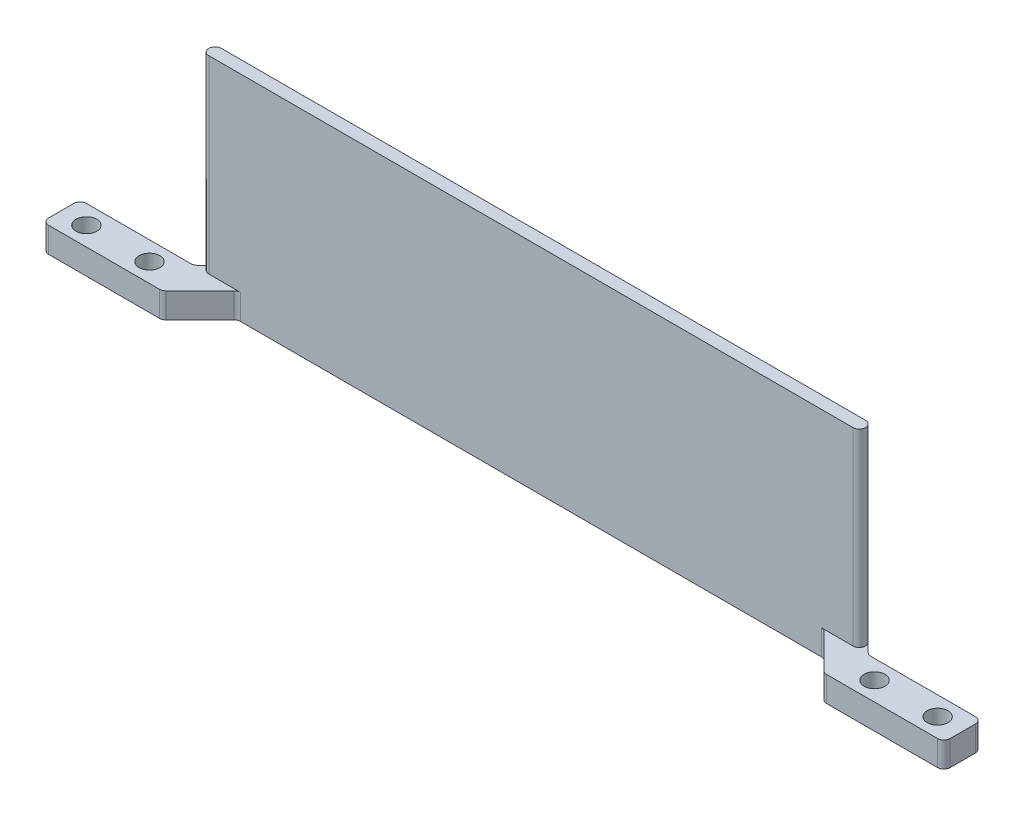
SolidWorks part; units mm, degrees
ref_plane "前视基准面" through (0, 0, 0) normal (0, 0, 1) x (1, 0, 0)
ref_plane "上视基准面" through (0, 0, 0) normal (0, 1, 0) x (1, 0, 0)
ref_plane "右视基准面" through (0, 0, 0) normal (1, 0, 0) x (0, 0, -1)
other "Configuration Table"
sketch "草图1" plane through (0, 0, 0) normal (0, 1, 0) x (1, 0, 0)
  line L0 (0, 0) -> (0, 13.6735) construction
  line L1 (-71.5, 3) -> (-71.5, -3)
  line L2 (-71.5, -3) -> (-52.5, -3)
  line L3 (-52.5, -3) -> (-46.5, 3)
  line L4 (-46.5, 3) -> (46.5, 3)
  line L5 (-51.5, 5) -> (51.5, 5)
  line L6 (-71.5, 3) -> (-53.5, 3)
  line L7 (51.5, 5) -> (53.5, 3)
  line L8 (-51.5, 5) -> (-53.5, 3)
  line L9 (71.5, 3) -> (53.5, 3)
  line L10 (52.5, -3) -> (46.5, 3)
  line L11 (71.5, -3) -> (52.5, -3)
  line L12 (71.5, 3) -> (71.5, -3)
  circle A0 centre (-57.5, 0) radius 1.65
  circle A1 centre (-67.5, 0) radius 1.65
  circle A4 centre (67.5, 0) radius 1.65
  circle A5 centre (57.5, 0) radius 1.65
  point P22 (0, 5)
  point P23 (0, 3)
  dimension "D1" = 3.3
  dimension "D4" = 4
  dimension "D2" = 10
  dimension "D3" = 57.5
  dimension "D5" = 3
  dimension "D6" = 3
  dimension "D7" = 4
  dimension "D8" = 135
  dimension "D9" = 2
  dimension "D10" = 5
extrude "凸台-拉伸1" add sketch "草图1" along normal blind 4
sketch "草图2" plane through (0, 4, 0) normal (0, 1, 0) x (1, 0, 0)
  line L0 (-51.5, 5) -> (-53.5, 3)
  line L1 (-53.5, 3) -> (53.5, 3)
  line L2 (53.5, 3) -> (51.5, 5)
  line L3 (51.5, 5) -> (-51.5, 5)
extrude "凸台-拉伸2" add sketch "草图2" along normal blind 30
fillet "圆角1" radius 1 12 edges at (51.5, 17, -5) (-51.5, 17, -5) (-71.5, 2, -3) (-71.5, 2, 3) (-46.5, 2, -3) (46.5, 2, -3) (52.5, 2, 3) (71.5, 2, 3) (71.5, 2, -3) (-52.5, 2, 3) (-53.5, 19, -3) (53.5, 19, -3)
fillet "圆角2" radius 1 2 edges at (53.5, 2, -3) (-53.5, 2, -3)
